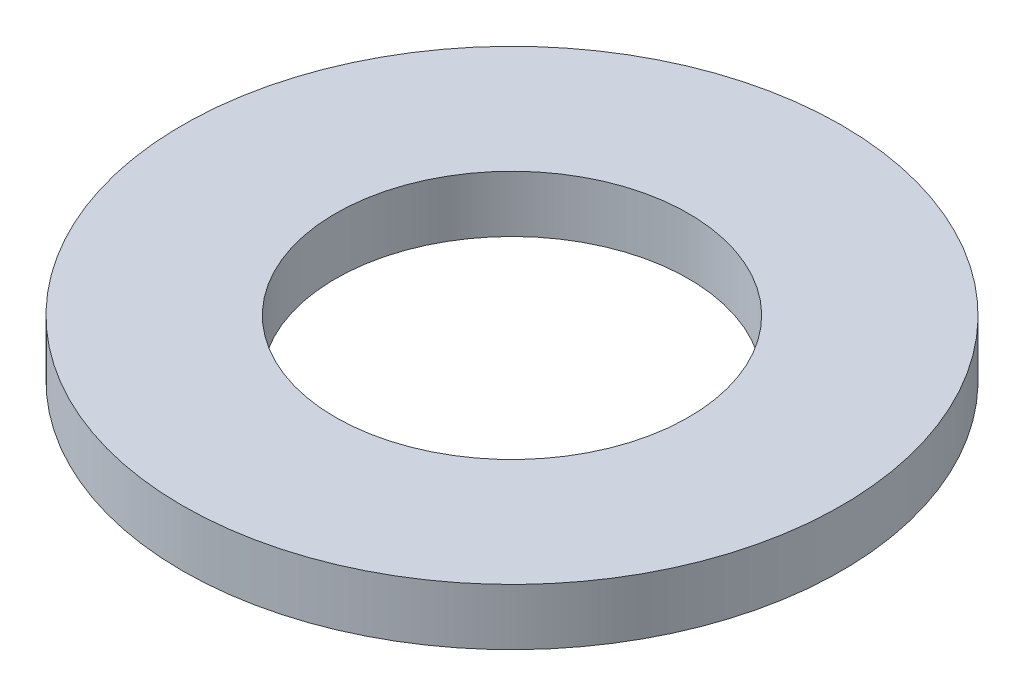
SolidWorks part; units mm, degrees
ref_plane "Front Plane" through (0, 0, 0) normal (0, 0, 1) x (1, 0, 0)
ref_plane "Top Plane" through (0, 0, 0) normal (0, 1, 0) x (1, 0, 0)
ref_plane "Right Plane" through (0, 0, 0) normal (1, 0, 0) x (0, 0, -1)
sketch "Sketch1" plane through (0, 0, 0) normal (0, 1, 0) x (1, 0, 0)
  circle A0 centre (0, 0) radius 70
  dimension "FLANGE_OD" = 140
extrude "Boss-Extrude1" add sketch "Sketch1" along normal blind 12
sketch "Sketch2" plane through (0, 0, 0) normal (0, 1, 0) x (1, 0, 0)
  circle A0 centre (0, 0) radius 37.5
  dimension "BORE_D" = 75
extrude "Cut-Extrude1" cut sketch "Sketch2" along normal through all
sketch "Sketch3" plane through (0, 12, 0) normal (0, 1, 0) x (1, 0, 0)
  circle A0 centre (0, 0) radius 23.2005 construction
  circle A1 centre (-23.2005, 0) radius 4.7825
  dimension "BOLT_D" = 9.565
  dimension "BOLT_PCD" = 46.401
extrude "Cut-Extrude2" cut sketch "Sketch3" against normal blind 10.1721 rebuild error yes
pattern_circular "CirPattern1" count 6 over 360 rebuild error yes
